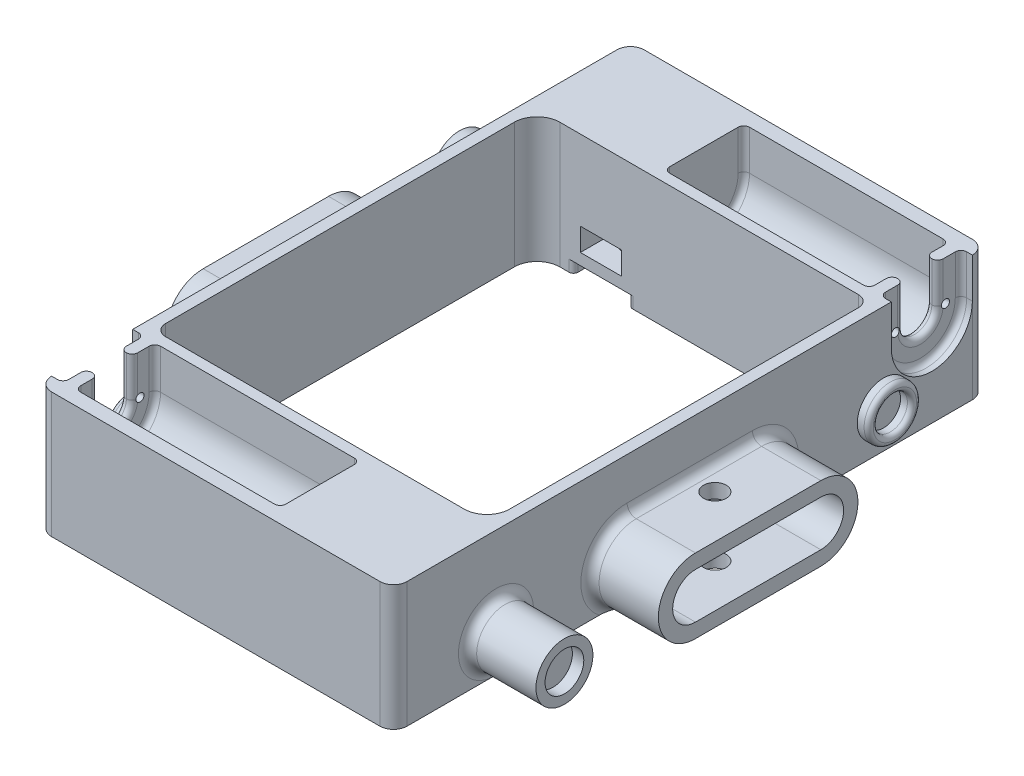
SolidWorks part; units mm, degrees
ref_plane "Front Plane" through (0, 0, 0) normal (0, 0, 1) x (1, 0, 0)
ref_plane "Top Plane" through (0, 0, 0) normal (0, 1, 0) x (1, 0, 0)
ref_plane "Right Plane" through (0, 0, 0) normal (1, 0, 0) x (0, 0, -1)
ref_axis "Center Axis" through (0, 23.7128, 0) along (0, -1, 0)
sketch "Sketch1" plane through (0, 0, 0) normal (1, 0, 0) x (0, 0, -1)
  line L0 (-159.8432, -20) -> (183.538, -20) construction
  line L1 (23.9696, -38.5304) -> (68.7681, 6.2681) construction
  line L2 (44.3566, -9.3934) -> (44.3566, -0.6434)
  line L3 (61.8566, -9.3934) -> (61.8566, -0.6434)
  line L4 (42, -0.6434) -> (42, -28.1434)
  line L5 (42, -28.1434) -> (65, -28.1434)
  line L6 (42, -0.6434) -> (44.3566, -0.6434)
  line L7 (61.8566, -0.6434) -> (65, -0.6434)
  line L8 (65, -28.1434) -> (65, -0.6434)
  arc A0 (44.3566, -9.3934) -> (61.8566, -9.3934) centre (53.1066, -9.3934) ccw
  point P1 (42.5, -20)
  dimension "D1" = 20
  dimension "D4" = 8.75
  dimension "D2" = 42.5
  dimension "D3" = 45
  dimension "D5" = 8.75
  dimension "D6" = 15
  dimension "D7" = 27.5
  dimension "D8" = 42
  dimension "D9" = 65
extrude "FrontMotorBracket" add sketch "Sketch1" along normal blind 45 from offset 11 offset against normal yes
sketch "Sketch8" plane through (0, 0, 0) normal (1, 0, 0) x (0, 0, -1)
  line L0 (-79.9426, -20) -> (109.5131, -20) construction
  line L1 (-68.835, 6.335) -> (-18.9148, -43.5852) construction
  line L2 (-61.8566, -9.3934) -> (-61.8566, -0.6434)
  line L3 (-65, -0.6434) -> (-65, -28.1434)
  line L4 (-44.3566, -0.6434) -> (-44.3566, -9.3934)
  line L5 (-65, -28.1434) -> (-42, -28.1434)
  line L6 (-65, -0.6434) -> (-61.8566, -0.6434)
  line L7 (-44.3566, -0.6434) -> (-42, -0.6434)
  line L8 (-42, -28.1434) -> (-42, -0.6434)
  arc A0 (-61.8566, -9.3934) -> (-44.3566, -9.3934) centre (-53.1066, -9.3934) ccw
  point P5 (-42.5, -20)
  dimension "D5" = 8.75
  dimension "D1" = 20
  dimension "D2" = 42.5
  dimension "D3" = 45
  dimension "D4" = 15
  dimension "D6" = 8.75
  dimension "D7" = 65
  dimension "D8" = 42
  dimension "D9" = 27.5
extrude "RearMotorBracket" add sketch "Sketch8" against normal blind 45 from offset 11 separate body
sketch "Sketch12" plane through (0, -28.1434, 0) normal (0, -1, 0) x (-1, 0, 0)
  line L0 (-34, 42) -> (11, 42) construction
  line L1 (-36.5, 39.5) -> (-36.5, -37)
  line L2 (0, 108.8981) -> (0, -169.353) construction
  line L3 (11, 65) -> (11, 42)
  line L4 (-11, -42) -> (-31.5, -42)
  line L5 (-39, 62) -> (-39, -62)
  line L6 (11, 65) -> (36, 65)
  line L7 (39, -62) -> (39, 62)
  line L8 (-34, 42) -> (-34, 65) construction
  line L9 (-34, 42) -> (-34, 65)
  line L10 (11, 42) -> (31.5, 42)
  line L11 (-36, 65) -> (-34, 65)
  line L12 (-11, -65) -> (-11, -42)
  line L13 (36.5, -39.5) -> (36.5, 37)
  line L14 (-165.3195, 0) -> (124.3922, 0) construction
  line L15 (34, -42) -> (34, -65)
  line L16 (36, -65) -> (34, -65)
  line L19 (-11, -65) -> (-36, -65)
  arc A0 (-34, 42) -> (-36.5, 39.5) centre (-34, 39.5) ccw
  arc A1 (-31.5, -42) -> (-36.5, -37) centre (-31.5, -37) cw
  arc A2 (36, 65) -> (39, 62) centre (36, 62) cw
  arc A3 (-36, -65) -> (-39, -62) centre (-36, -62) cw
  arc A4 (31.5, 42) -> (36.5, 37) centre (31.5, 37) cw
  arc A5 (34, -42) -> (36.5, -39.5) centre (34, -39.5) ccw
  arc A6 (39, -62) -> (36, -65) centre (36, -62) cw
  arc A8 (-39, 62) -> (-36, 65) centre (-36, 62) cw
  point P40 (0, 0)
  dimension "D2" = 36.5
  dimension "D3" = 5
  dimension "D4" = 2
  dimension "D8" = 3
  dimension "D6" = 3
  dimension "D1" = 2.5
extrude "FrameExtrude" add sketch "Sketch12" against normal up to surface (27.5 mm away) up to face at (-11.5, -0.6434, 43.1783)
sketch "Sketch18" plane through (-39, 0, 0) normal (-1, 0, 0) x (0, 0, 1)
  line L1 (62, -9.3934) -> (62, -0.6434)
  line L3 (44.2132, -9.3934) -> (44.2132, -0.6434)
  line L4 (44.2132, -0.6434) -> (62, -0.6434)
  line L6 (62, -0.6434) -> (-62, -0.6434) construction
  line L7 (62, -0.6434) -> (62, -28.1434) construction
  arc A0 (44.2132, -9.3934) -> (62, -9.3934) centre (53.1066, -9.3934) ccw
  arc A2 (44.3566, -9.3934) -> (61.8566, -9.3934) centre (53.1066, -9.3934) ccw construction
extrude "GearCut" cut sketch "Sketch18" against normal blind 2.5
sketch "Sketch19" plane through (-36.5, 0, 0) normal (-1, 0, 0) x (0, 0, 1)
  line L0 (49.3566, -9.3934) -> (49.3566, -0.6434)
  line L2 (49.3566, -0.6434) -> (56.8566, -0.6434)
  line L3 (56.8566, -0.6434) -> (56.8566, -9.3934)
  line L4 (62, -0.6434) -> (44.2132, -0.6434) construction
  arc A0 (49.3566, -9.3934) -> (56.8566, -9.3934) centre (53.1066, -9.3934) ccw
  arc A1 (44.2132, -9.3934) -> (62, -9.3934) centre (53.1066, -9.3934) ccw construction
  dimension "D1" = 7.5
extrude "MotorCut" cut sketch "Sketch19" against normal up to next
sketch "Sketch20" plane through (-36.5, 0, 0) normal (-1, 0, 0) x (0, 0, 1)
  line L0 (53.1066, 7.9232) -> (53.1066, -34.4496) construction
  line L1 (56.8566, -9.3934) -> (56.8566, -0.6434) construction
  line L2 (49.3566, -0.6434) -> (49.3566, -9.3934) construction
  circle A0 centre (47.6066, -9.3934) radius 0.875
  circle A1 centre (58.6066, -9.3934) radius 0.875
  dimension "D1" = 1.75
  dimension "D2" = 11
extrude "MotorScrewHoles" cut sketch "Sketch20" against normal up to next
sketch "Sketch14" plane through (-39, 0, 0) normal (-1, 0, 0) x (0, 0, 1)
  line L0 (55.855, -6.645) -> (41.5591, -20.9409) construction
  line L1 (62, -28.1434) -> (-62, -28.1434) construction
  circle A0 centre (42.5, -20) radius 5.75
  arc A1 (49.3566, -9.3934) -> (56.8566, -9.3934) centre (53.1066, -9.3934) ccw construction
  arc A3 (49.3566, -9.3934) -> (56.8566, -9.3934) centre (53.1066, -9.3934) ccw construction
  dimension "D1" = 45
  dimension "D2" = 11.5
  dimension "D3" = 15
extrude "DrivenBearingExtrude" add sketch "Sketch14" along normal blind 2.5
sketch "Sketch31" plane through (-41.5, 0, 0) normal (-1, 0, 0) x (0, 0, 1)
  circle A0 centre (42.5, -20) radius 3.75
  circle A1 centre (42.5, -20) radius 5.75 construction
  dimension "D1" = 7.5
extrude "DrivenBearingCut" cut sketch "Sketch31" against normal blind 2.5
sketch "Sketch32" plane through (-39, 0, 0) normal (-1, 0, 0) x (0, 0, 1)
  circle A0 centre (42.5, -20) radius 1.75
  circle A1 centre (42.5, -20) radius 3.75 construction
  dimension "D1" = 3.5
extrude "DrivenShaftCut" cut sketch "Sketch32" against normal blind 1
sketch "Sketch22" plane through (-39, 0, 0) normal (-1, 0, 0) x (0, 0, 1)
  circle A2 centre (42.5, -20) radius 3.75 construction
  circle A3 centre (-42.5, -20) radius 6.25
  circle A4 centre (42.5, -20) radius 3.75 construction
  dimension "D1" = 12.5
  dimension "D2" = 85
extrude "PassiveBearingExtrude" add sketch "Sketch22" along normal blind 15
sketch "Sketch23" plane through (-54, 0, 0) normal (-1, 0, 0) x (0, 0, 1)
  circle A0 centre (-42.5, -20) radius 4.25
  circle A3 centre (-42.5, -20) radius 6.25 construction
  dimension "D1" = 8.5
extrude "PassiveBearingCut" cut sketch "Sketch23" against normal blind 2.5
sketch "Sketch24" plane through (-39, 0, 0) normal (-1, 0, 0) x (0, 0, 1)
  line L0 (62, -28.1434) -> (-62, -28.1434) construction
  line L1 (0, 14.312) -> (0, -42.5044) construction
  line L2 (-13.75, -11.8566) -> (13.75, -11.8566)
  line L3 (-42.5, -20) -> (42.5, -20) construction
  line L4 (-13.75, -28.1434) -> (13.75, -28.1434)
  arc A0 (-13.75, -28.1434) -> (-13.75, -11.8566) centre (-13.75, -20) cw
  arc A1 (13.75, -11.8566) -> (13.75, -28.1434) centre (13.75, -20) cw
  dimension "D1" = 27.5
extrude "SidePlateConnectorExtrude" add sketch "Sketch24" along normal blind 15
sketch "Sketch25" plane through (-54, 0, 0) normal (-1, 0, 0) x (0, 0, 1)
  line L0 (-13.75, -15) -> (13.75, -15)
  line L1 (-13.75, -25) -> (13.75, -25)
  arc A0 (-13.75, -15) -> (-13.75, -25) centre (-13.75, -20) ccw
  arc A1 (-13.75, -11.8566) -> (-13.75, -28.1434) centre (-13.75, -20) ccw construction
  arc A2 (13.75, -15) -> (13.75, -25) centre (13.75, -20) cw
  arc A3 (13.75, -28.1434) -> (13.75, -11.8566) centre (13.75, -20) ccw construction
  dimension "D1" = 10
extrude "SidePlateConnectorCut" cut sketch "Sketch25" against normal blind 15
sketch "Sketch26" plane through (0, -11.8566, 0) normal (0, 1, 0) x (1, 0, 0)
  line L0 (-39, -13.75) -> (-39, 13.75) construction
  line L1 (28.3188, 0) -> (-93.0586, 0) construction
  circle A0 centre (-44.5, 0) radius 2.5
  dimension "D2" = 5
  dimension "D1" = 5.5
extrude "SidePlateConnectorHole" cut sketch "Sketch26" against normal through all
sketch "Sketch27" plane through (0, -28.1434, 0) normal (0, -1, 0) x (-1, 0, 0)
  line L0 (-22.5, -90.9247) -> (-22.5, 80.5229) construction
  line L1 (130.232, 0) -> (-91.8964, 0) construction
  line L2 (-18, -42) -> (-18, -52.0981)
  line L3 (34, -42) -> (-31.5, -42) construction
  line L4 (-18, -52.0981) -> (-22.5, -54.6962)
  line L5 (-22.5, -54.6962) -> (-27, -52.0981)
  line L6 (-27, -52.0981) -> (-27, -42)
  line L7 (-18, -42) -> (-27, -42)
  circle A0 centre (-22.5, -49.5) radius 4.5 construction
  dimension "D1" = 7.5
  dimension "D2" = 9
  dimension "D3" = 120
  dimension "D4" = 22.5
extrude "BatteryHolderNutInsert" cut sketch "Sketch27" against normal blind 5 from offset 5 offset against normal yes
sketch "Sketch28" plane through (0, -28.1434, 0) normal (0, -1, 0) x (-1, 0, 0)
  line L0 (-22.5, -84.3787) -> (-22.5, 82.4006) construction
  line L1 (-28.5, -49.5) -> (-28.5, -43)
  line L2 (34, -42) -> (-31.5, -42) construction
  line L3 (-16.5, -49.5) -> (-16.5, -43)
  line L4 (-15.5, -42) -> (-29.5, -42)
  arc A0 (-16.5, -49.5) -> (-28.5, -49.5) centre (-22.5, -49.5) cw
  arc A1 (-28.5, -43) -> (-29.5, -42) centre (-29.5, -43) ccw
  arc A2 (-16.5, -43) -> (-15.5, -42) centre (-15.5, -43) cw
  dimension "D4" = 1
  dimension "D5" = 1
  dimension "D1" = 22.5
  dimension "D2" = 12
  dimension "D3" = 7.5
extrude "BatteryHolderAttachmentPoint" cut sketch "Sketch28" against normal blind 2.5
sketch "Sketch29" plane through (0, -25.6434, 0) normal (0, -1, 0) x (-1, 0, 0)
  circle A0 centre (-22.5, -49.5) radius 2.75
  arc A1 (-28.5, -49.5) -> (-16.5, -49.5) centre (-22.5, -49.5) ccw construction
  dimension "D1" = 5.5
extrude "BatteryHolderBoltHole" cut sketch "Sketch29" against normal blind 10
pattern_circular "PlaceOtherMotorFeatures" count 2 over 360 about axis through (0, 23.7128, 0) along (0, -1, 0) of "GearCut", "MotorCut", "MotorScrewHoles", "DrivenBearingExtrude", "DrivenBearingCut", "PassiveBearingExtrude", "PassiveBearingCut", "SidePlateConnectorExtrude", "SidePlateConnectorCut", "SidePlateConnectorHole"
pattern_circular "PlaceOtherBatteryHolderFeatures" count 2 over 360 about axis through (0, 23.7128, 0) along (0, -1, 0) of "BatteryHolderNutInsert", "BatteryHolderAttachmentPoint", "BatteryHolderBoltHole"
fillet "Fillet125" radius 1.25 30 edges at (-36.5, -5.0184, 44.2132) (-36.5, -5.0184, 62) (-34, -5.0184, 44.3566) (-34, -5.0184, 61.8566) (11, -5.0184, 44.3566) (11, -5.0184, 61.8566) (-36.5, -18.2868, 53.1066) (-34, -18.1434, 53.1066) (11, -18.1434, 53.1066) (-34, -5.0184, 56.8566) (-34, -13.1434, 53.1066) (-36.5, -5.0184, 56.8566) (-36.5, -13.1434, 53.1066) (-34, -5.0184, 49.3566) (-36.5, -5.0184, 49.3566) (36.5, -5.0184, -44.2132) (36.5, -5.0184, -62) (34, -5.0184, -61.8566) (34, -5.0184, -44.3566) (-11, -5.0184, -61.8566) (-11, -5.0184, -44.3566) (36.5, -18.2868, -53.1066) (34, -18.1434, -53.1066) (-11, -18.1434, -53.1066) (34, -5.0184, -49.3566) (34, -5.0184, -56.8566) (36.5, -5.0184, -49.3566) (36.5, -5.0184, -56.8566) (34, -13.1434, -53.1066) (36.5, -13.1434, -53.1066)
fillet "Fillet100" radius 1 4 edges at (-41.5, -20, 48.25) (-41.5, -20, 46.25) (41.5, -20, -46.25) (41.5, -20, -48.25)
fillet "Fillet200" radius 2 8 edges at (-39, -20, 21.8934) (-39, -20, -21.8934) (-39, -20, -36.25) (-39, -11.8566, 0) (39, -20, -21.8934) (39, -20, 21.8934) (39, -20, 36.25) (39, -11.8566, 0)
